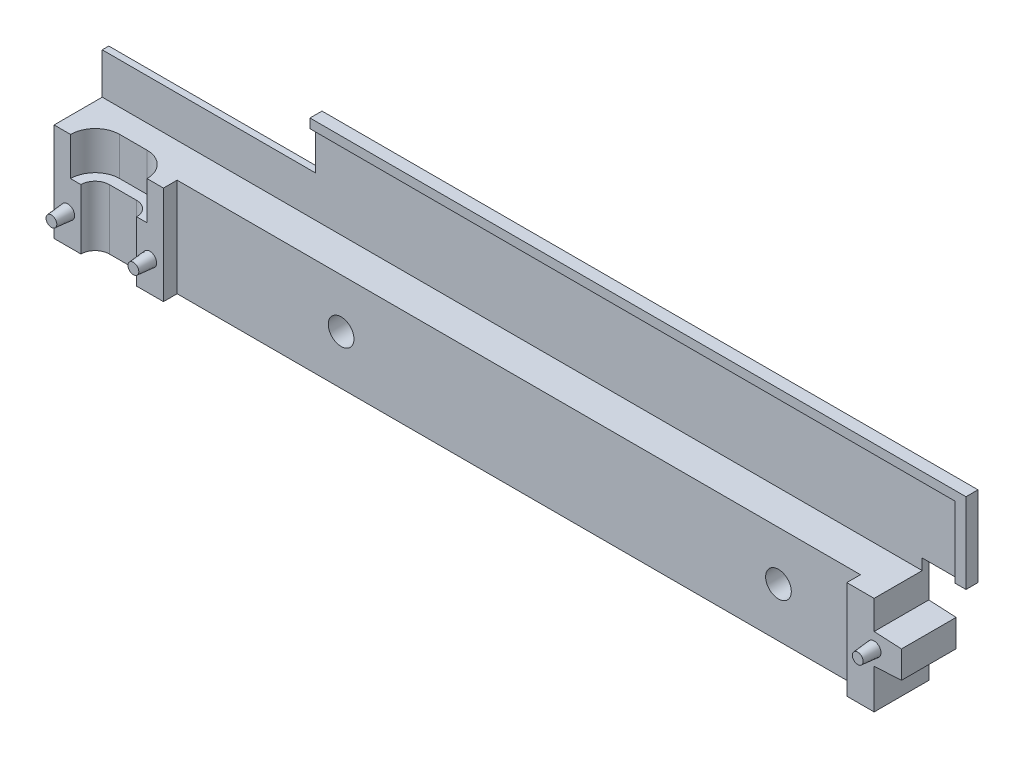
SolidWorks part; units mm, degrees
ref_plane "Front Plane" through (0, 0, 0) normal (0, 0, 1) x (1, 0, 0)
ref_plane "Top Plane" through (0, 0, 0) normal (0, 1, 0) x (1, 0, 0)
ref_plane "Right Plane" through (0, 0, 0) normal (1, 0, 0) x (0, 0, -1)
ref_axis "X-Axis" through (0, 0, 0) along (1, 0, 0)
ref_axis "Y-Axis" through (0, 42.2917, 0) along (0, -1, 0)
ref_axis "Z-Axis" through (0, 0, 55.0015) along (0, 0, -1)
sketch "Sketch1" plane through (0, 0, 0) normal (0, 0, 1) x (1, 0, 0)
  line L1 (-127.8191, -9.8629) -> (22.1809, -9.8629)
  line L2 (22.1809, -9.8629) -> (22.1809, -2.6129)
  line L3 (22.1809, -2.6129) -> (27.1809, -2.6129)
  line L4 (27.1809, -2.6129) -> (27.1809, 2.8871)
  line L5 (27.1809, 2.8871) -> (22.1809, 2.8871)
  line L6 (22.1809, 2.8871) -> (22.1809, 10.1371)
  line L7 (22.1809, 10.1371) -> (31.1809, 10.1371)
  line L8 (31.1809, 10.1371) -> (31.1809, 23.6371)
  line L10 (-127.8191, 15.6371) -> (-127.8191, -9.8629)
  line L12 (-88.8191, -25.8695) -> (-88.8191, 48.9262) construction
  line L13 (31.1809, 13.1371) -> (10.3885, 13.1371) construction
  line L14 (31.1809, 23.6371) -> (-88.8191, 23.6371) construction
  line L15 (-88.8191, 23.6371) -> (-88.8191, 15.6371)
  line L16 (-88.8191, 15.6371) -> (-127.8191, 15.6371)
  line L17 (31.1809, 23.6371) -> (31.1809, 24.8371)
  line L18 (31.1809, 24.8371) -> (-88.8191, 24.8371)
  line L19 (-88.8191, 24.8371) -> (-88.8191, 23.6371)
  point P5 (27.1809, 0.1371)
  dimension "D2" = 10
  dimension "D3" = 20
  dimension "D4" = 5.5
  dimension "D5" = 9
  dimension "D7" = 120
  dimension "D8" = 5
  dimension "D10" = 3
  dimension "D11" = 8
  dimension "D12" = 10.5
  dimension "D13" = 1.2
  dimension "D14" = 150
extrude "Boss-Extrude1" add sketch "Sketch1" along normal blind 10 and the other way blind 10
sketch "Sketch2" plane through (-127.8191, 0, 0) normal (-1, 0, 0) x (0, 0, 1)
  line L0 (-10, -9.8629) -> (10, -9.8629) construction
  line L1 (-8.8, 23.1371) -> (8.8, 23.1371) construction
  line L2 (-8.8, 23.1371) -> (-8.8, 8.1371)
  line L3 (-8.8, 8.1371) -> (8.8, 8.1371)
  line L4 (8.8, 23.1371) -> (8.8, 8.1371)
  line L5 (-10, 24.8371) -> (-10, 15.6371) construction
  line L7 (-10, 2.8871) -> (10, 2.8871) construction
  line L8 (-10, 15.6371) -> (-10, -9.8629) construction
  line L9 (10, 15.6371) -> (10, -9.8629) construction
  line L10 (0, 2.8871) -> (0, 23.1371) construction
  line L11 (-8.8, 23.1371) -> (-7.8, 23.1371)
  line L12 (-7.8, 23.1371) -> (-7.8, 24.8371)
  line L13 (-10, 24.8371) -> (10, 24.8371) construction
  line L14 (-7.8, 24.8371) -> (7.8, 24.8371)
  line L15 (7.8, 24.8371) -> (7.8, 23.1371)
  line L16 (7.8, 23.1371) -> (8.8, 23.1371)
  point P6 (0, 23.1371)
  dimension "D1" = 33
  dimension "D2" = 18
  dimension "D3" = 1
  dimension "D4" = 1
  dimension "D5" = 15
  dimension "D7" = 1.2
extrude "Cut-Extrude1" cut sketch "Sketch2" against normal offset from surface (157 mm away) 2 up to face at (31.1809, 17.4871, 0)
sketch "Sketch8" plane through (0, 0, 0) normal (0, 0, 1) x (1, 0, 0)
  line L0 (-127.8191, 15.6371) -> (-127.8191, -9.8629) construction
  line L1 (-107.8191, 24.8371) -> (17.1809, 24.8371)
  line L2 (-107.8191, 24.8371) -> (-107.8191, -9.8629)
  line L3 (-107.8191, -9.8629) -> (17.1809, -9.8629)
  line L4 (17.1809, 24.8371) -> (17.1809, -9.8629)
  line L5 (-127.8191, -9.8629) -> (22.1809, -9.8629) construction
  line L7 (22.1809, 2.8871) -> (22.1809, 10.1371) construction
  line L8 (29.1809, 24.8371) -> (-88.8191, 24.8371) construction
  point P12 (22.1809, 6.5121)
  dimension "D1" = 20
  dimension "D2" = 5
extrude "Cut-Extrude4" cut sketch "Sketch8" against normal blind 2.5 and the other way blind 2.5 contours L2 L3 L4 L1
sketch "Sketch9" plane through (0, 0, 0) normal (0, 0, 1) x (1, 0, 0)
  line L0 (-107.8191, -0.8629) -> (17.1809, -0.8629) construction
  line L1 (-107.8191, 8.1371) -> (-107.8191, -9.8629) construction
  line L2 (17.1809, 8.1371) -> (17.1809, -9.8629) construction
  circle A0 centre (-77.8191, -0.8629) radius 2.35
  circle A1 centre (2.1809, -0.8629) radius 2.35
  dimension "D1" = 4.7
  dimension "D2" = 80
  dimension "D3" = 15
extrude "Cut-Extrude5" cut sketch "Sketch9" against normal through all and the other way through all
chamfer "Chamfer2" distance 5 angle 3 2 edges at (27.1809, -2.6129, 0) (27.1809, 2.8871, 0) first distance on face at (24.6809, -2.6129, 0) first distance on face at (24.6809, 2.8871, 0)
sketch "Sketch14" plane through (0, 8.1371, 0) normal (0, 1, 0) x (1, 0, 0)
  line L0 (-120.3191, 4.5) -> (-115.3191, 4.5)
  line L1 (-115.3191, -4.5) -> (-120.3191, -4.5)
  line L2 (-107.8191, 0) -> (-127.8191, 0) construction
  line L3 (-107.8191, 2.5) -> (-107.8191, -2.5) construction
  line L5 (-127.8191, 8.8) -> (-127.8191, -8.8) construction
  arc A0 (-115.3191, 4.5) -> (-115.3191, -4.5) centre (-115.3191, 0) cw
  arc A1 (-120.3191, -4.5) -> (-120.3191, 4.5) centre (-120.3191, 0) cw
  point P16 (-117.8191, 0)
  dimension "D1" = 4.5
  dimension "D2" = 5
  dimension "D3" = 2.5
extrude "Cut-Extrude8" cut sketch "Sketch14" against normal blind 7
sketch "Sketch15" plane through (0, 1.1371, 0) normal (0, 1, 0) x (1, 0, 0)
  line L7 (-120.3191, -2.6) -> (-115.3191, -2.6)
  line L8 (-115.3191, 2.6) -> (-120.3191, 2.6)
  arc A2 (-120.3191, 4.5) -> (-120.3191, -4.5) centre (-120.3191, 0) ccw construction
  arc A3 (-115.3191, -4.5) -> (-115.3191, 4.5) centre (-115.3191, 0) ccw construction
  arc A6 (-120.3191, 2.6) -> (-120.3191, -2.6) centre (-120.3191, 0) ccw
  arc A7 (-115.3191, -2.6) -> (-115.3191, 2.6) centre (-115.3191, 0) ccw
  dimension "D2" = 2.6
extrude "Cut-Extrude9" cut sketch "Sketch15" against normal through all
sketch "Sketch16" plane through (0, 0, 0) normal (0, 0, 1) x (1, 0, 0)
  line L1 (-137.4451, 59.0989) -> (76.8996, 59.0989)
  line L2 (-137.4451, 59.0989) -> (-137.4451, -25.5467)
  line L3 (-137.4451, -25.5467) -> (76.8996, -25.5467)
  line L4 (76.8996, 59.0989) -> (76.8996, -25.5467)
extrude "Cut-Extrude10" cut sketch "Sketch16" along normal through all
sketch "Sketch17" plane through (0, 0, 0) normal (0, 0, 1) x (1, 0, 0)
  line L1 (31.1809, 24.8371) -> (29.1809, 24.8371)
  line L2 (31.1809, 24.8371) -> (31.1809, 10.1371)
  line L3 (31.1809, 10.1371) -> (29.1809, 10.1371)
  line L4 (29.1809, 24.8371) -> (29.1809, 10.1371)
extrude "Cut-Extrude11" cut sketch "Sketch17" against normal up to surface (7.8 mm away) up to face at (-29.8191, 23.9871, -7.8)
sketch "Sketch19" plane through (0, 0, 0) normal (0, 0, 1) x (1, 0, 0)
  line L0 (17.1809, 0.1371) -> (27.1809, 0.1371) construction
  line L1 (27.1809, 2.6251) -> (27.1809, -2.3509) construction
  line L3 (-125.3191, -4.3629) -> (-110.3191, -4.3629) construction
  line L5 (-117.8191, -9.8629) -> (-117.8191, 1.1371) construction
  line L8 (17.1809, 8.1371) -> (17.1809, -9.8629) construction
  line L11 (-115.3191, -9.8629) -> (-120.3191, -9.8629) construction
  line L12 (-115.3191, 1.1371) -> (-120.3191, 1.1371) construction
  circle A0 centre (-125.3191, -4.3629) radius 1.25
  circle A1 centre (-110.3191, -4.3629) radius 1.25
  circle A2 centre (22.1809, 0.1371) radius 1.25
  point P17 (-117.8191, -4.3629)
  dimension "D2" = 2.5
  dimension "D1" = 15
extrude "Boss-Extrude5" add sketch "Sketch19" along normal blind 3 separate body
chamfer "Chamfer3" distance 3 angle 5 1 edges at (23.4309, 0.1371, 3) first distance on face at (23.4309, 0.1371, 3)
chamfer "Chamfer4" distance 3 angle 5 1 edges at (-109.0691, -4.3629, 3) first distance on face at (-109.0691, -4.3629, 3)
chamfer "Chamfer5" distance 3 angle 5 1 edges at (-124.0691, -4.3629, 3) first distance on face at (-124.0691, -4.3629, 3)
equation "\"Largeur Bande\"= 16.3"
equation "\"Largeur Feeder\"= \"Largeur Rail\" + 1.2 + 1.2 + 0.3"
equation "\"Largeur Rail\"= \"Largeur Bande\" + 1"
equation "\"D1@Boss-Extrude1\"=\"Largeur Feeder\"/2"
equation "\"D2@Boss-Extrude1\"=\"Largeur Feeder\"/2"
